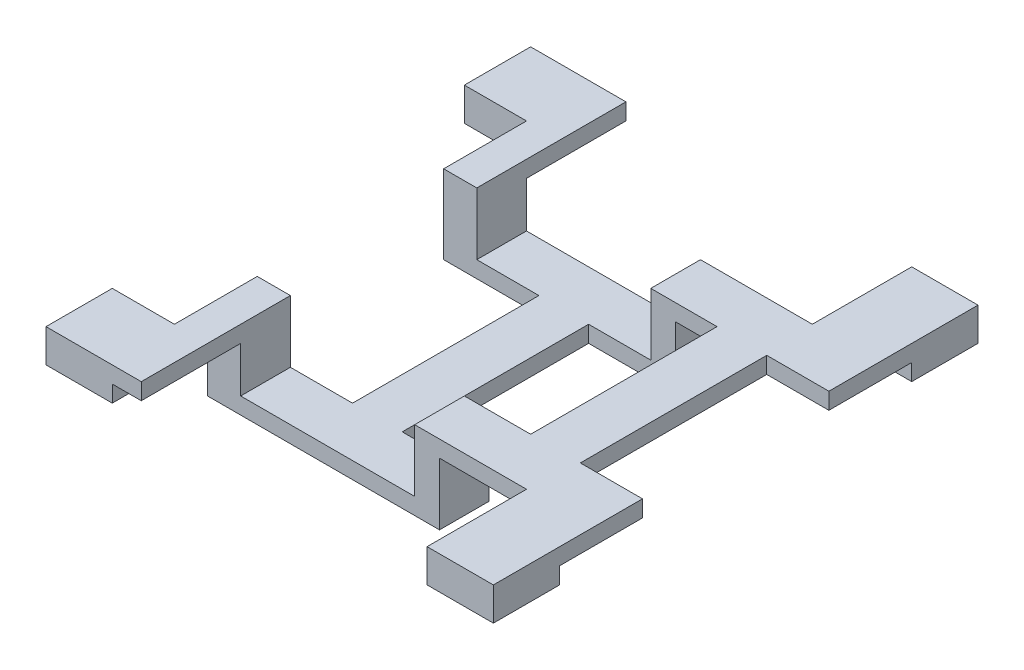
SolidWorks part; units mm, degrees
ref_plane "Front Plane" through (0, 0, 0) normal (0, 0, 1) x (1, 0, 0)
ref_plane "Top Plane" through (0, 0, 0) normal (0, 1, 0) x (1, 0, 0)
ref_plane "Right Plane" through (0, 0, 0) normal (1, 0, 0) x (0, 0, -1)
sketch "Sketch1" plane through (0, 0, 0) normal (0, 1, 0) x (1, 0, 0)
  line L1 (-56.5, 42.5) -> (56.5, 42.5)
  line L2 (-56.5, 42.5) -> (-56.5, -42.5)
  line L3 (-56.5, -42.5) -> (56.5, -42.5)
  line L4 (56.5, 42.5) -> (56.5, -42.5)
  line L5 (-56.5, 42.5) -> (56.5, -42.5) construction
  line L6 (-56.5, -42.5) -> (56.5, 42.5) construction
  point P0 (0, 0)
  dimension "D1" = 113
  dimension "D2" = 85
extrude "Boss-Extrude1" add sketch "Sketch1" along normal blind 4
sketch "Sketch4" plane through (0, 0, 0) normal (0, -1, 0) x (1, 0, 0)
  line L0 (-56.5, 42.5) -> (56.5, 42.5) construction
  line L5 (-56.5, 42.5) -> (-40.5, 42.5)
  line L6 (-56.5, 42.5) -> (-56.5, 58.5)
  line L7 (-56.5, 58.5) -> (-40.5, 58.5)
  line L8 (-40.5, 42.5) -> (-40.5, 58.5)
  line L9 (51.5, 42.5) -> (35.5, 42.5)
  line L10 (51.5, 42.5) -> (51.5, 58.5)
  line L11 (51.5, 58.5) -> (35.5, 58.5)
  line L12 (35.5, 42.5) -> (35.5, 58.5)
  line L18 (56.5, 42.5) -> (56.5, -42.5) construction
  line L19 (0, 0) -> (-56.5, 0) construction
  line L20 (-56.5, -42.5) -> (-56.5, 42.5) construction
  line L21 (51.5, -58.5) -> (35.5, -58.5)
  line L22 (35.5, -42.5) -> (35.5, -58.5)
  line L23 (51.5, -42.5) -> (35.5, -42.5)
  line L24 (51.5, -42.5) -> (51.5, -58.5)
  line L25 (-56.5, -58.5) -> (-40.5, -58.5)
  line L26 (-40.5, -42.5) -> (-40.5, -58.5)
  line L27 (-56.5, -42.5) -> (-40.5, -42.5)
  line L28 (-56.5, -42.5) -> (-56.5, -58.5)
  dimension "D1" = 16
  dimension "D2" = 16
  dimension "D3" = 5
  dimension "D4" = 16
  dimension "D5" = 16
extrude "Boss-Extrude3" add sketch "Sketch4" against normal up to surface (4 mm away) and the other way blind 1 up to face at (0, 4, 0)
sketch "Sketch10" plane through (0, 4, 0) normal (0, 1, 0) x (1, 0, 0)
  line L0 (-40.5, -58.5) -> (-56.5, -58.5) construction
  line L1 (-40.5, -42.5) -> (-30.5, -42.5)
  line L2 (-40.5, -42.5) -> (-40.5, -58.5)
  line L3 (-40.5, -58.5) -> (-30.5, -58.5)
  line L4 (-30.5, -42.5) -> (-30.5, -58.5)
  line L5 (-40.5, 42.5) -> (-30.5, 42.5)
  line L6 (-40.5, 42.5) -> (-40.5, 58.5)
  line L7 (-40.5, 58.5) -> (-30.5, 58.5)
  line L8 (-30.5, 42.5) -> (-30.5, 58.5)
  line L9 (-56.5, 58.5) -> (-40.5, 58.5) construction
  dimension "D1" = 10
  dimension "D2" = 10
extrude "Boss-Extrude6" add sketch "Sketch10" against normal up to surface (4 mm away) up to face at (9.3, 0, 0)
sketch "Sketch6" plane through (0, 4, 0) normal (0, 1, 0) x (1, 0, 0)
  line L0 (35.5, 42.5) -> (35.5, 58.5) construction
  line L1 (-31.5, 22.5) -> (41.5, 22.5)
  line L2 (-31.5, 22.5) -> (-31.5, -22.5)
  line L3 (-31.5, -22.5) -> (41.5, -22.5)
  line L4 (41.5, 22.5) -> (41.5, -22.5)
  line L5 (35.5, -58.5) -> (35.5, -42.5) construction
  line L6 (35.5, 42.5) -> (-30.5, 42.5) construction
  line L7 (-30.5, -42.5) -> (35.5, -42.5) construction
  line L8 (-56.5, 58.5) -> (-56.5, -58.5) construction
  line L9 (-41.5, 0) -> (-56.5, 0) construction
  line L10 (-56.5, 42.5) -> (-41.5, 42.5)
  line L11 (-56.5, 42.5) -> (-56.5, -42.5)
  line L12 (-56.5, -42.5) -> (-41.5, -42.5)
  line L13 (-41.5, 42.5) -> (-41.5, -42.5)
  line L14 (-31.5, 0) -> (41.5, 0) construction
  line L15 (-30.5, 42.5) -> (35.5, 42.5)
  line L16 (-30.5, 42.5) -> (-30.5, 34.5)
  line L17 (-30.5, 34.5) -> (35.5, 34.5)
  line L18 (35.5, 42.5) -> (35.5, 34.5)
  line L19 (-30.5, -42.5) -> (35.5, -42.5)
  line L20 (-30.5, -42.5) -> (-30.5, -34.5)
  line L21 (-30.5, -34.5) -> (35.5, -34.5)
  line L22 (35.5, -42.5) -> (35.5, -34.5)
  line L23 (56.5, -42.5) -> (56.5, 42.5) construction
  dimension "D1" = 20
  dimension "D2" = 20
  dimension "D3" = 25
  dimension "D4" = 15
  dimension "D5" = 85
  dimension "D6" = 8
  dimension "D7" = 8
  dimension "D8" = 15
extrude "Cut-Extrude2" cut sketch "Sketch6" against normal through all
sketch "Sketch8" plane through (0, -1, 0) normal (0, -1, 0) x (1, 0, 0)
  line L0 (-56.5, 58.5) -> (-40.5, 58.5) construction
  line L1 (-56.5, 58.5) -> (-56.5, 42.5) construction
  line L2 (-56.5, 42.5) -> (-40.5, 42.5) construction
  line L3 (-40.5, 58.5) -> (-40.5, 42.5) construction
  line L4 (35.5, 58.5) -> (51.5, 58.5) construction
  line L5 (35.5, 58.5) -> (35.5, 42.5) construction
  line L6 (35.5, 42.5) -> (51.5, 42.5) construction
  line L7 (51.5, 58.5) -> (51.5, 42.5) construction
  line L8 (-56.5, 58.5) -> (-40.5, 42.5) construction
  line L9 (-56.5, 42.5) -> (-40.5, 58.5) construction
  line L10 (35.5, 58.5) -> (51.5, 42.5) construction
  line L11 (35.5, 42.5) -> (51.5, 58.5) construction
  line L12 (51.5, 58.5) -> (35.5, 58.5) construction
  line L13 (0, 0) -> (-56.5, 0) construction
  line L14 (-56.5, 42.5) -> (-40.5, 42.5) construction
  line L15 (35.5, 42.5) -> (51.5, 42.5) construction
  circle A0 centre (-48.5, 50.5) radius 6.1
  circle A1 centre (43.5, 50.5) radius 6.1
  circle A2 centre (43.5, -50.5) radius 6.1
  circle A3 centre (-48.5, -50.5) radius 6.1
  dimension "D3" = 12.2
  dimension "D4" = 12.2
extrude "Cut-Extrude3" cut sketch "Sketch8" against normal blind 3.2
sketch "Sketch9" plane through (0, -1, 0) normal (0, -1, 0) x (1, 0, 0)
  line L0 (-55.5, 57.5) -> (-55.5, 43.5)
  line L1 (-56.5, 58.5) -> (-40.5, 58.5)
  line L2 (-56.5, 58.5) -> (-56.5, 42.5)
  line L3 (-56.5, 42.5) -> (-40.5, 42.5)
  line L4 (-40.5, 58.5) -> (-40.5, 42.5)
  line L5 (35.5, 58.5) -> (51.5, 58.5)
  line L6 (35.5, 58.5) -> (35.5, 42.5)
  line L7 (35.5, 42.5) -> (51.5, 42.5)
  line L8 (51.5, 58.5) -> (51.5, 42.5)
  line L9 (-55.5, 43.5) -> (-41.5, 43.5)
  line L10 (-41.5, 57.5) -> (-41.5, 43.5)
  line L11 (-55.5, 57.5) -> (-41.5, 57.5)
  line L16 (0, 0) -> (-56.5, 0) construction
  line L17 (36.5, -43.5) -> (50.5, -43.5)
  line L18 (36.5, -57.5) -> (36.5, -43.5)
  line L19 (50.5, -57.5) -> (36.5, -57.5)
  line L20 (50.5, 43.5) -> (50.5, 57.5)
  line L21 (50.5, 57.5) -> (36.5, 57.5)
  line L22 (36.5, 57.5) -> (36.5, 43.5)
  line L23 (36.5, 43.5) -> (50.5, 43.5)
  line L24 (50.5, 43.5) -> (50.5, 57.5)
  line L25 (50.5, 57.5) -> (36.5, 57.5)
  line L26 (36.5, 57.5) -> (36.5, 43.5)
  line L27 (36.5, 43.5) -> (50.5, 43.5)
  line L28 (50.5, -43.5) -> (50.5, -57.5)
  line L29 (-55.5, -57.5) -> (-41.5, -57.5)
  line L30 (-41.5, -57.5) -> (-41.5, -43.5)
  line L31 (-55.5, -43.5) -> (-41.5, -43.5)
  line L32 (51.5, -58.5) -> (51.5, -42.5)
  line L33 (35.5, -42.5) -> (51.5, -42.5)
  line L34 (35.5, -58.5) -> (35.5, -42.5)
  line L35 (35.5, -58.5) -> (51.5, -58.5)
  line L36 (-40.5, -58.5) -> (-40.5, -42.5)
  line L37 (-56.5, -42.5) -> (-40.5, -42.5)
  line L38 (-56.5, -58.5) -> (-56.5, -42.5)
  line L39 (-56.5, -58.5) -> (-40.5, -58.5)
  line L40 (-55.5, -57.5) -> (-55.5, -43.5)
  dimension "D1" = 1
  dimension "D2" = 1
extrude "Boss-Extrude5" add sketch "Sketch9" along normal blind 3
fillet "Fillet1" radius 0.2 4 edges at (43.5, -1, -44.4) (-48.5, -1, -44.4) (43.5, -1, 44.4) (-48.5, -1, 44.4)
sketch "Sketch13" plane through (56.5, 0, 0) normal (1, 0, 0) x (0, 0, -1)
  line L1 (-42.5, 4) -> (42.5, 4)
  line L2 (-42.5, 4) -> (-42.5, 0)
  line L3 (-42.5, 0) -> (42.5, 0)
  line L4 (42.5, 4) -> (42.5, 0)
extrude "Cut-Extrude4" cut sketch "Sketch13" against normal up to surface (5 mm away) up to face at (51.5, 0, 48.9)
sketch "Sketch14" plane through (0, 4, 0) normal (0, 1, 0) x (1, 0, 0)
  line L0 (-41.5, -42.5) -> (-41.5, 42.5) construction
  line L1 (-41.5, 22.5) -> (51.5, 22.5)
  line L2 (-41.5, 22.5) -> (-41.5, -22.5)
  line L3 (-41.5, -22.5) -> (51.5, -22.5)
  line L4 (51.5, 22.5) -> (51.5, -22.5)
  line L5 (51.5, 58.5) -> (51.5, -58.5) construction
  line L6 (-31.5, -22.5) -> (41.5, -22.5) construction
  line L7 (41.5, 22.5) -> (-31.5, 22.5) construction
extrude "Cut-Extrude5" cut sketch "Sketch14" against normal through all
sketch "Sketch15" plane through (0, 4, 0) normal (0, 1, 0) x (1, 0, 0)
  line L0 (51.5, 22.5) -> (-41.5, 22.5) construction
  line L1 (-18.5, 22.5) -> (-6.5, 22.5)
  line L2 (-18.5, 22.5) -> (-18.5, -22.5)
  line L3 (-18.5, -22.5) -> (-6.5, -22.5)
  line L4 (-6.5, 22.5) -> (-6.5, -22.5)
  line L5 (-41.5, -22.5) -> (51.5, -22.5) construction
  line L6 (51.5, -22.5) -> (51.5, -58.5) construction
  line L7 (24.5, 22.5) -> (36.5, 22.5)
  line L8 (24.5, 22.5) -> (24.5, -22.5)
  line L9 (24.5, -22.5) -> (36.5, -22.5)
  line L10 (36.5, 22.5) -> (36.5, -22.5)
  line L11 (-41.5, -42.5) -> (-41.5, -22.5) construction
  dimension "D1" = 12
  dimension "D2" = 12
  dimension "D3" = 15
  dimension "D4" = 23
extrude "Boss-Extrude7" add sketch "Sketch15" against normal up to surface (4 mm away) up to face at (-5.1, 0, 40.1)
sketch "Sketch16" plane through (0, 0, 0) normal (0, -1, 0) x (1, 0, 0)
  line L24 (24.5, 22.5) -> (24.5, -22.5) construction
  line L25 (24.5, -22.5) -> (-6.5, -22.5) construction
  line L26 (-6.5, -22.5) -> (-6.5, 22.5) construction
  line L27 (-6.5, 22.5) -> (24.5, 22.5) construction
  line L28 (24.5, 22.5) -> (24.5, -22.5) construction
  line L29 (24.5, -22.5) -> (-6.5, -22.5) construction
  line L30 (-6.5, -22.5) -> (-6.5, 22.5)
  line L31 (-6.5, 22.5) -> (24.5, 22.5) construction
  line L36 (-30.5, -34.5) -> (14.5, -34.5)
  line L37 (14.5, -34.5) -> (14.5, -22.5)
  line L38 (14.5, -22.5) -> (-6.5, -22.5)
  line L39 (-6.5, 22.5) -> (14.5, 22.5)
  line L40 (14.5, 22.5) -> (14.5, 34.5)
  line L41 (14.5, 34.5) -> (-30.5, 34.5)
  line L42 (-18.5, 22.5) -> (-41.5, 22.5)
  line L43 (-41.5, 22.5) -> (-18.5, 22.5) construction
  line L44 (-41.5, 22.5) -> (-41.5, 34.5)
  line L45 (-41.5, 34.5) -> (-30.5, 34.5)
  line L46 (-18.5, -22.5) -> (-41.5, -22.5)
  line L47 (-18.5, -22.5) -> (-41.5, -22.5) construction
  line L48 (-41.5, 42.5) -> (-41.5, 22.5)
  line L49 (-41.5, 22.5) -> (-18.5, 22.5)
  line L50 (-18.5, 22.5) -> (-18.5, -22.5)
  line L51 (-18.5, -22.5) -> (-41.5, -22.5)
  line L52 (-41.5, -22.5) -> (-41.5, -42.5)
  line L53 (-41.5, -42.5) -> (-40.5, -42.5)
  line L54 (-40.5, -42.5) -> (-40.5, -58.5)
  line L55 (-40.5, -58.5) -> (-30.5, -58.5)
  line L56 (-30.5, -58.5) -> (-30.5, -34.5)
  line L57 (-30.5, -34.5) -> (35.5, -34.5)
  line L58 (35.5, -34.5) -> (35.5, -42.5)
  line L59 (35.5, -42.5) -> (51.5, -42.5)
  line L60 (51.5, -42.5) -> (51.5, -22.5)
  line L61 (51.5, -22.5) -> (36.5, -22.5)
  line L62 (36.5, -22.5) -> (36.5, 22.5)
  line L63 (36.5, 22.5) -> (51.5, 22.5)
  line L64 (51.5, 22.5) -> (51.5, 42.5)
  line L65 (51.5, 42.5) -> (35.5, 42.5)
  line L66 (35.5, 42.5) -> (35.5, 34.5)
  line L67 (35.5, 34.5) -> (-30.5, 34.5)
  line L68 (-30.5, 34.5) -> (-30.5, 58.5)
  line L69 (-30.5, 58.5) -> (-40.5, 58.5)
  line L70 (-40.5, 58.5) -> (-40.5, 42.5)
  line L71 (-40.5, 42.5) -> (-41.5, 42.5)
  line L72 (-41.5, 42.5) -> (-41.5, 22.5) construction
  line L74 (-18.5, 22.5) -> (-18.5, -22.5)
  line L76 (-41.5, -22.5) -> (-41.5, -42.5) construction
  line L77 (-41.5, -42.5) -> (-40.5, -42.5) construction
  line L78 (-40.5, -42.5) -> (-40.5, -58.5) construction
  line L79 (-40.5, -58.5) -> (-30.5, -58.5) construction
  line L80 (-30.5, -58.5) -> (-30.5, -34.5) construction
  line L81 (-30.5, -34.5) -> (35.5, -34.5) construction
  line L82 (35.5, -34.5) -> (35.5, -42.5) construction
  line L83 (35.5, -42.5) -> (51.5, -42.5) construction
  line L84 (51.5, -42.5) -> (51.5, -22.5) construction
  line L85 (51.5, -22.5) -> (36.5, -22.5) construction
  line L86 (36.5, -22.5) -> (36.5, 22.5) construction
  line L87 (36.5, 22.5) -> (51.5, 22.5) construction
  line L88 (51.5, 22.5) -> (51.5, 42.5) construction
  line L89 (51.5, 42.5) -> (35.5, 42.5) construction
  line L90 (35.5, 42.5) -> (35.5, 34.5) construction
  line L91 (35.5, 34.5) -> (-30.5, 34.5) construction
  line L92 (-30.5, 34.5) -> (-30.5, 58.5) construction
  line L93 (-30.5, 58.5) -> (-40.5, 58.5) construction
  line L94 (-40.5, 58.5) -> (-40.5, 42.5) construction
  line L95 (-40.5, 42.5) -> (-41.5, 42.5) construction
  line L96 (-41.5, -22.5) -> (-41.5, -34.5)
  line L97 (-41.5, -34.5) -> (-30.5, -34.5)
  dimension "D2" = 45
  dimension "D1" = 0
extrude "Boss-Extrude8" add sketch "Sketch16" along normal blind 15
sketch "Sketch17" plane through (0, 4, 0) normal (0, 1, 0) x (1, 0, 0)
  line L0 (-30.5, -58.5) -> (-56.5, -58.5) construction
  line L1 (-33.5, 58.5) -> (8.5, 58.5)
  line L2 (-33.5, 58.5) -> (-33.5, -58.5)
  line L3 (-33.5, -58.5) -> (8.5, -58.5)
  line L4 (8.5, 58.5) -> (8.5, -58.5)
  line L7 (-41.5, 22.5) -> (-41.5, 42.5) construction
  line L8 (-56.5, 58.5) -> (-30.5, 58.5) construction
  point P10 (8.5, -34.5)
  dimension "D1" = 8
  dimension "D2" = 42
extrude "Cut-Extrude6" cut sketch "Sketch17" against normal blind 15
